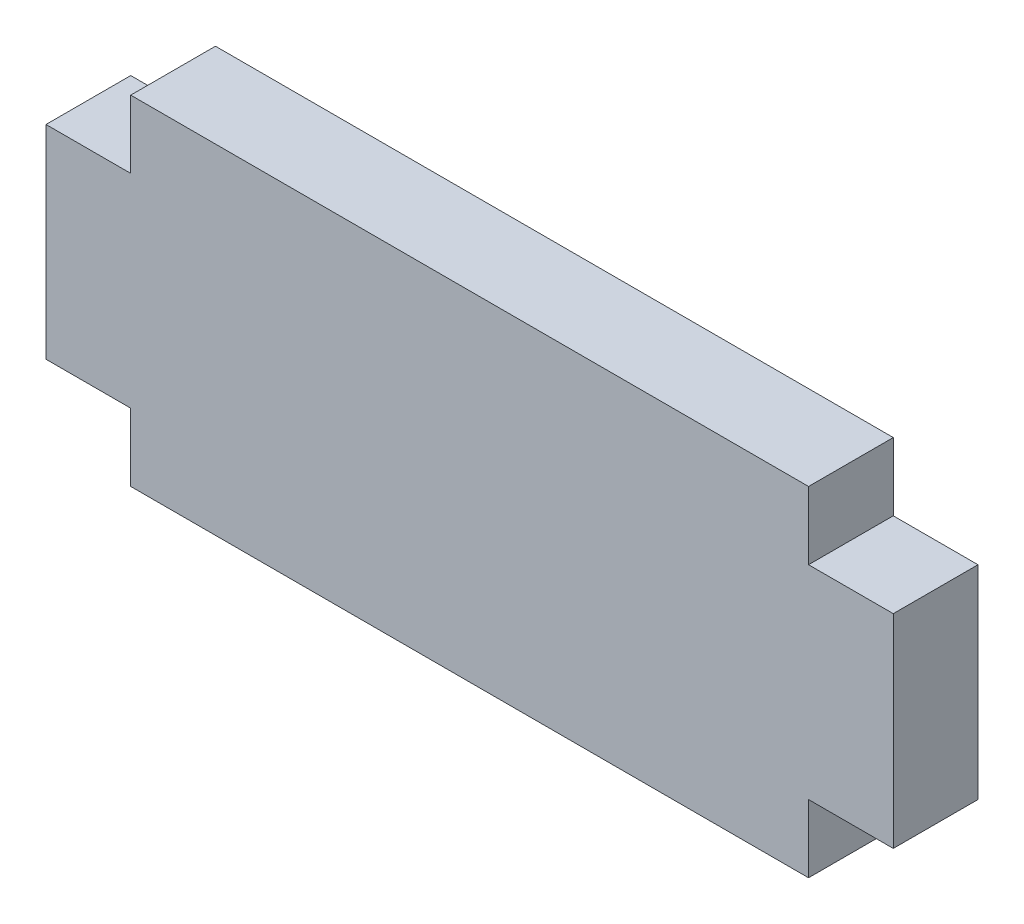
SolidWorks part; units mm, degrees
ref_plane "Front Plane" through (0, 0, 0) normal (0, 0, 1) x (1, 0, 0)
ref_plane "Top Plane" through (0, 0, 0) normal (0, 1, 0) x (1, 0, 0)
ref_plane "Right Plane" through (0, 0, 0) normal (1, 0, 0) x (0, 0, -1)
sketch "Sketch1" plane through (0, 0, 0) normal (0, 0, 1) x (1, 0, 0)
  line L1 (0, 0) -> (25.4, 0)
  line L2 (0, 0) -> (0, 12.7)
  line L3 (0, 12.7) -> (25.4, 12.7)
  line L4 (25.4, 0) -> (25.4, 12.7)
  dimension "D1" = 25.4
  dimension "D2" = 12.7
extrude "Boss-Extrude1" add sketch "Sketch1" along normal blind 3.175
sketch "Sketch2" plane through (0, 0, 3.175) normal (0, 0, 1) x (1, 0, 0)
  line L0 (0, 12.7) -> (0, 0) construction
  line L1 (0, 10.16) -> (-3.175, 10.16)
  line L2 (0, 10.16) -> (0, 2.54)
  line L3 (0, 2.54) -> (-3.175, 2.54)
  line L4 (-3.175, 10.16) -> (-3.175, 2.54)
  line L5 (12.7, 12.7) -> (12.7, 0) construction
  line L6 (25.4, 12.7) -> (0, 12.7) construction
  line L7 (0, 0) -> (25.4, 0) construction
  line L8 (25.4, 2.54) -> (28.575, 2.54)
  line L9 (25.4, 10.16) -> (25.4, 2.54)
  line L10 (25.4, 10.16) -> (28.575, 10.16)
  line L11 (28.575, 10.16) -> (28.575, 2.54)
  point P6 (0, 6.35)
  point P7 (-3.175, 6.35)
  dimension "D1" = 7.62
  dimension "D2" = 3.175
extrude "Boss-Extrude2" add sketch "Sketch2" against normal blind 3.175
